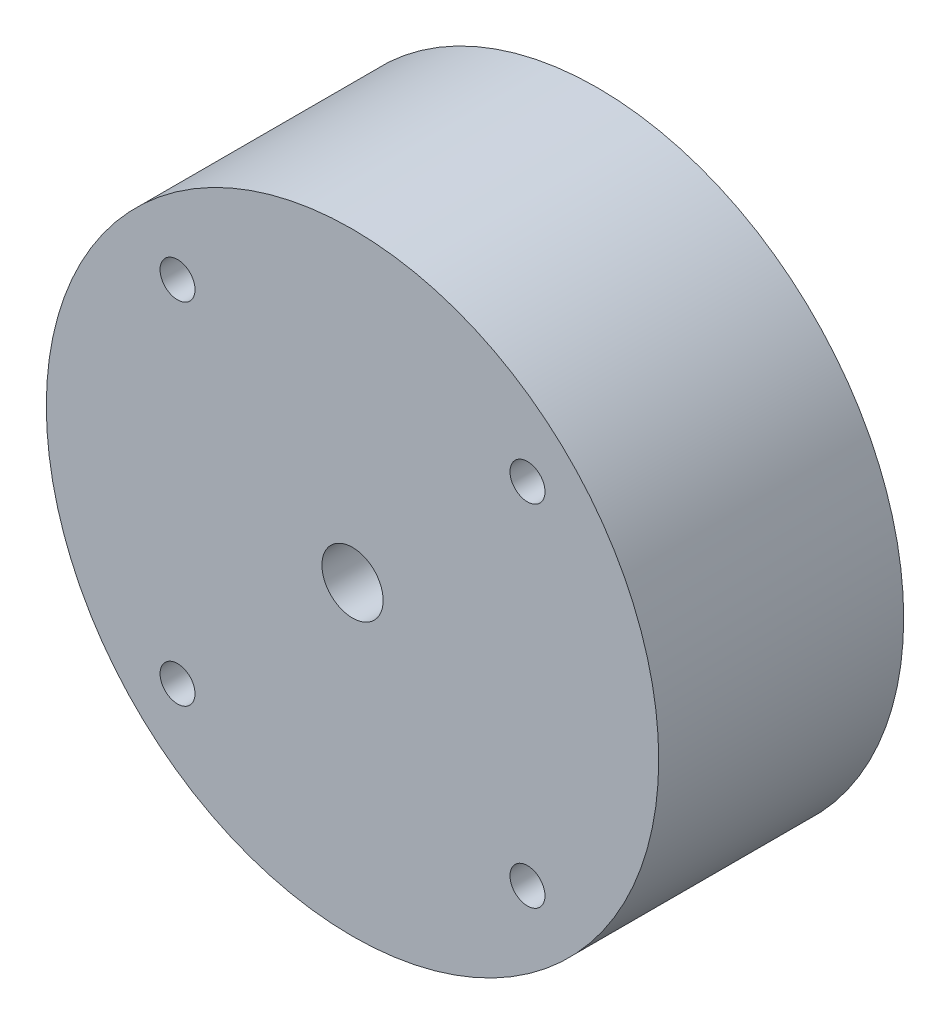
SolidWorks part; units mm, degrees
ref_plane "Front Plane" through (0, 0, 0) normal (0, 0, 1) x (1, 0, 0)
ref_plane "Top Plane" through (0, 0, 0) normal (0, 1, 0) x (1, 0, 0)
ref_plane "Right Plane" through (0, 0, 0) normal (1, 0, 0) x (0, 0, -1)
sketch "Sketch1" plane through (0, 0, 0) normal (0, 0, 1) x (1, 0, 0)
  circle A0 centre (0, 0) radius 17.5
  circle A1 centre (0, 0) radius 1.75
  dimension "D1" = 35
  dimension "D2" = 3.5
extrude "Boss-Extrude1" add sketch "Sketch1" along normal blind 14
sketch "Sketch2" plane through (0, 0, 14) normal (0, 0, 1) x (1, 0, 0)
  circle A0 centre (0, 13.45) radius 1
  dimension "D1" = 2
  dimension "D2" = 13.45
extrude "Cut-Extrude1" [suppressed] cut sketch "Sketch2" against normal through all
pattern_circular "CirPattern1" [suppressed] count 4 over 360 of bodies 102
sketch "Sketch3" plane through (0, 0, 14) normal (0, 0, 1) x (1, 0, 0)
  line L0 (-10, 0) -> (-10, -10) construction
  line L1 (0, 0) -> (-17.5, 0) construction
  circle A0 centre (-10, -10) radius 1
  circle A3 centre (0, 0) radius 17.5 construction
  dimension "D1" = 2
  dimension "D2" = 10
  dimension "D3" = 10
extrude "Cut-Extrude2" cut sketch "Sketch3" against normal through all
pattern_circular "CirPattern2" count 4 over 360 about axis through (0, 0, 14) along (0, 0, 1) of "Cut-Extrude2"
